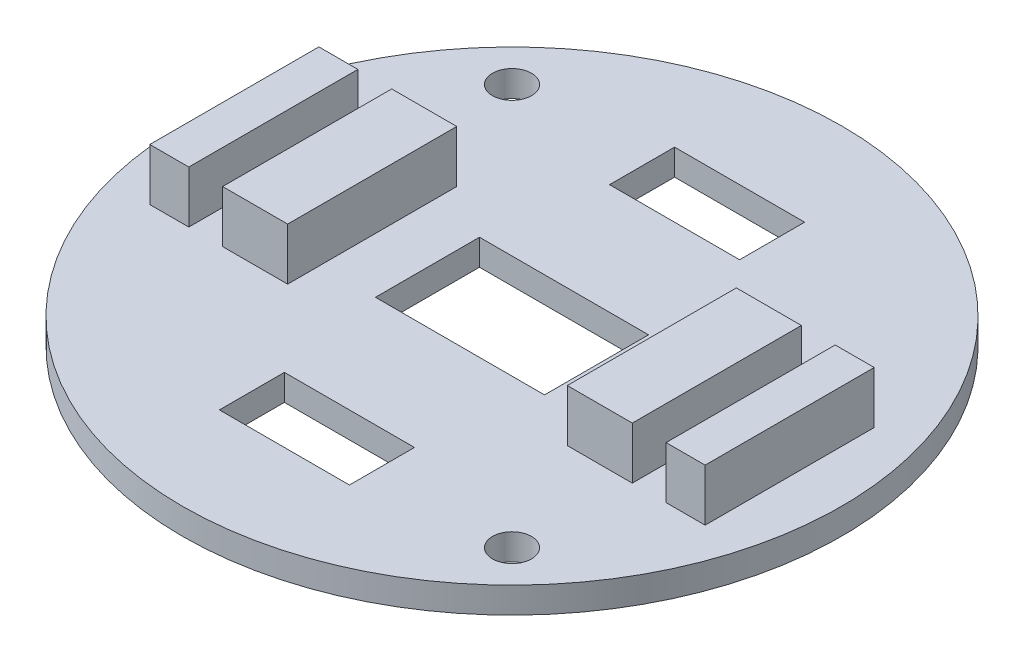
SolidWorks part; units mm, degrees
ref_plane "Front Plane" through (0, 0, 0) normal (0, 0, 1) x (1, 0, 0)
ref_plane "Top Plane" through (0, 0, 0) normal (0, 1, 0) x (1, 0, 0)
ref_plane "Right Plane" through (0, 0, 0) normal (1, 0, 0) x (0, 0, -1)
sketch "Sketch1" plane through (0, 0, 0) normal (0, 1, 0) x (1, 0, 0)
  circle A0 centre (0, 0) radius 25.34
  dimension "D1" = 50.68
extrude "Boss-Extrude1" add sketch "Sketch1" along normal blind 2
sketch "Sketch2" plane through (0, 2, 0) normal (0, 1, 0) x (1, 0, 0)
  line L0 (-15.75, 0) -> (15.75, 0) construction
  line L1 (0, 32.0817) -> (0, -28.5676) construction
  line L10 (10.75, -6.5) -> (15.75, -6.5)
  line L11 (10.75, -6.5) -> (10.75, 6.5)
  line L12 (10.75, 6.5) -> (15.75, 6.5)
  line L13 (15.75, -6.5) -> (15.75, 6.5)
  line L22 (21.35, 6.5) -> (18.35, 6.5)
  line L23 (21.35, 6.5) -> (21.35, -6.5)
  line L24 (21.35, -6.5) -> (18.35, -6.5)
  line L25 (18.35, 6.5) -> (18.35, -6.5)
  line L26 (21.35, 6.5) -> (18.35, -6.5) construction
  line L27 (21.35, -6.5) -> (18.35, 6.5) construction
  line L28 (-21.35, -6.5) -> (-18.35, -6.5)
  line L29 (-18.35, 6.5) -> (-18.35, -6.5)
  line L30 (-21.35, 6.5) -> (-18.35, 6.5)
  line L31 (-21.35, 6.5) -> (-21.35, -6.5)
  line L32 (-21.35, -6.5) -> (-18.35, 6.5) construction
  line L33 (-21.35, 6.5) -> (-18.35, -6.5) construction
  line L34 (-10.75, 6.5) -> (-15.75, 6.5)
  line L35 (-15.75, -6.5) -> (-15.75, 6.5)
  line L36 (-10.75, -6.5) -> (-15.75, -6.5)
  line L37 (-10.75, -6.5) -> (-10.75, 6.5)
  point P2 (0, 0)
  point P7 (15.75, 0)
  point P8 (19.85, 0)
  point P13 (-19.85, 0)
  dimension "D1" = 31.5
  dimension "D2" = 13
  dimension "D3" = 5
  dimension "D4" = 3
  dimension "D5" = 2.6
extrude "Boss-Extrude2" add sketch "Sketch2" along normal blind 4
sketch "Sketch3" plane through (0, 2, 0) normal (0, 1, 0) x (1, 0, 0)
  line L0 (-15.422, 15.422) -> (15.422, -15.422) construction
  line L1 (-43.7486, 0) -> (48.7139, 0) construction
  circle A0 centre (-15.422, 15.422) radius 1.5
  circle A1 centre (15.422, -15.422) radius 1.5
  point P6 (0, 0)
  dimension "D3" = 3
  dimension "D1" = 45
  dimension "D2" = 43.62
extrude "Cut-Extrude1" cut sketch "Sketch3" against normal through all
sketch "Sketch4" plane through (0, 2, 0) normal (0, 1, 0) x (1, 0, 0)
  line L0 (-60.1037, 0) -> (65.0626, 0) construction
  line L1 (5, 17.5) -> (-5, 17.5)
  line L2 (5, 17.5) -> (5, 12.5)
  line L3 (5, 12.5) -> (-5, 12.5)
  line L4 (-5, 17.5) -> (-5, 12.5)
  line L5 (5, 17.5) -> (-5, 12.5) construction
  line L6 (5, 12.5) -> (-5, 17.5) construction
  line L7 (5, -12.5) -> (-5, -17.5) construction
  line L8 (5, -17.5) -> (-5, -12.5) construction
  line L9 (-5, -17.5) -> (-5, -12.5)
  line L10 (5, -12.5) -> (-5, -12.5)
  line L11 (5, -17.5) -> (5, -12.5)
  line L12 (5, -17.5) -> (-5, -17.5)
  line L14 (6.5, 4) -> (-6.5, 4)
  line L15 (6.5, 4) -> (6.5, -4)
  line L16 (6.5, -4) -> (-6.5, -4)
  line L17 (-6.5, 4) -> (-6.5, -4)
  line L18 (6.5, 4) -> (-6.5, -4) construction
  line L19 (6.5, -4) -> (-6.5, 4) construction
  point P0 (0, 15)
  point P12 (0, -15)
  point P13 (0, 0)
  dimension "D1" = 10
  dimension "D2" = 5
  dimension "D3" = 15
  dimension "D4" = 13
  dimension "D5" = 8
extrude "Cut-Extrude2" cut sketch "Sketch4" against normal through all
